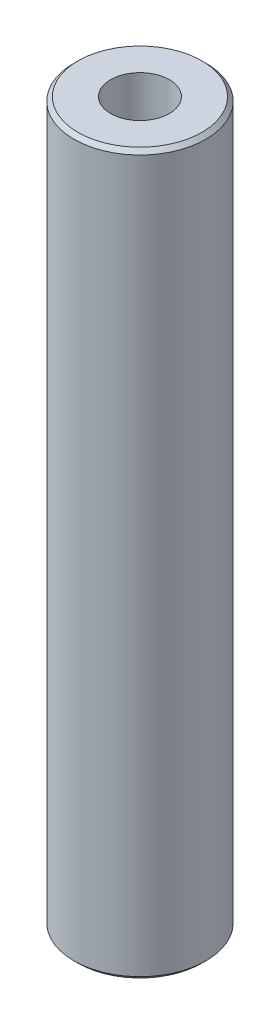
SolidWorks part; units mm, degrees
ref_plane "Front Plane" through (0, 0, 0) normal (0, 0, 1) x (1, 0, 0)
ref_plane "Top Plane" through (0, 0, 0) normal (0, 1, 0) x (1, 0, 0)
ref_plane "Right Plane" through (0, 0, 0) normal (1, 0, 0) x (0, 0, -1)
sketch "Sketch1" plane through (0, 0, 0) normal (0, 1, 0) x (1, 0, 0)
  circle A0 centre (0, 0) radius 55
  dimension "SHAFT_OD" = 110
extrude "Boss-Extrude1" add sketch "Sketch1" along normal blind 600
sketch "Sketch2" plane through (0, 0, 0) normal (0, 1, 0) x (1, 0, 0)
  circle A0 centre (0, 0) radius 24.4886
  dimension "BORE_D" = 48.9772
extrude "Cut-Extrude1" cut sketch "Sketch2" along normal through all
chamfer "Chamfer1" distance 3.3214 angle 45 2 edges at (0, 600, 55) (0, 0, 55)
